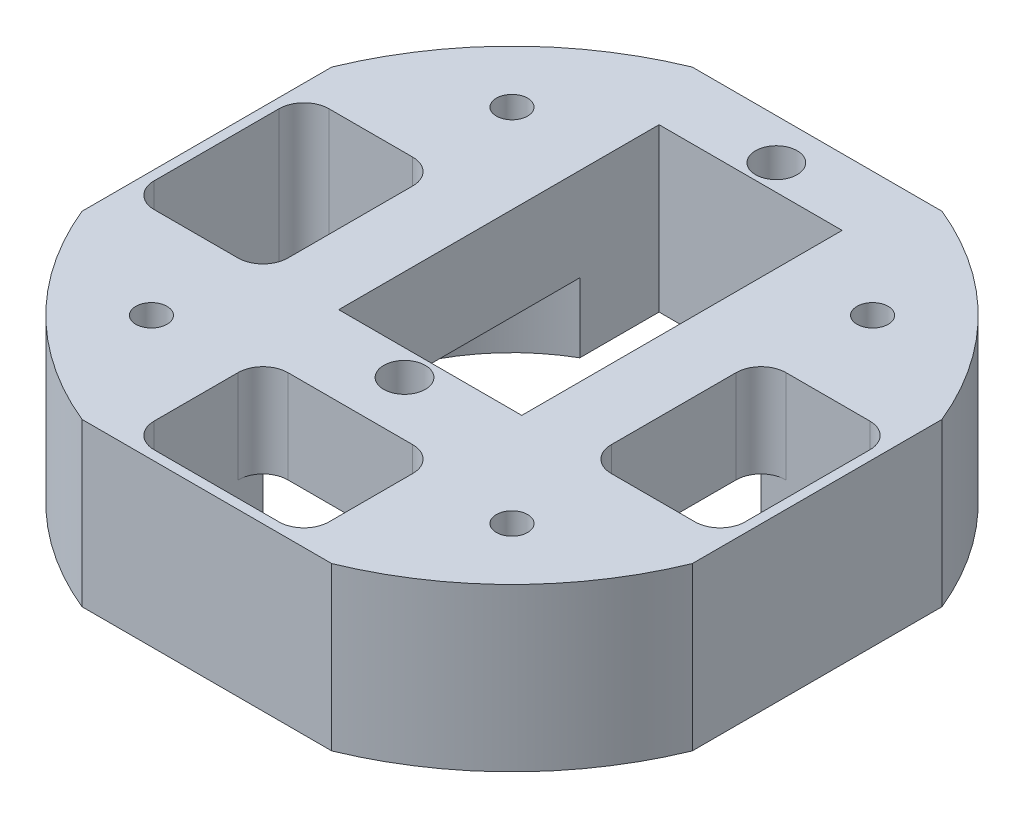
SolidWorks part; units mm, degrees
ref_plane "Front Plane" through (0, 0, 0) normal (0, 0, 1) x (1, 0, 0)
ref_plane "Top Plane" through (0, 0, 0) normal (0, 1, 0) x (1, 0, 0)
ref_plane "Right Plane" through (0, 0, 0) normal (1, 0, 0) x (0, 0, -1)
sketch "Sketch2" plane through (0, 0, 0) normal (0, 1, 0) x (1, 0, 0)
  line L0 (17, -17) -> (-17, -17)
  line L1 (17, -17) -> (17, 17)
  line L2 (17, 17) -> (-17, 17)
  line L3 (-17, -17) -> (-17, 17)
  line L4 (-4.5, -19.5) -> (-1.5, -19.5) construction
  line L5 (-1.5, -19.5) -> (1.5, -19.5) construction
  line L6 (-22, -22) -> (22, -22)
  line L7 (-10.5, 13) -> (-10.5, 17)
  line L8 (-13, 10.5) -> (-17, 10.5)
  line L9 (-10.5, -13) -> (-10.5, -17)
  line L10 (-13, -10.5) -> (-17, -10.5)
  line L11 (10.5, -13) -> (10.5, -17)
  line L12 (13, -10.5) -> (17, -10.5)
  line L13 (13, 10.5) -> (17, 10.5)
  line L14 (10.5, 13) -> (10.5, 17)
  line L15 (-22, -22) -> (-22, 22)
  line L16 (-22, 22) -> (22, 22)
  line L17 (22, -22) -> (22, 22)
  line L18 (-22, -22) -> (22, 22) construction
  line L19 (-22, 22) -> (22, -22) construction
  line L20 (1.5, -19.5) -> (4.5, -19.5) construction
  line L21 (-19.5, 4.5) -> (-19.5, 1.5) construction
  line L22 (-19.5, 1.5) -> (-19.5, -1.5) construction
  line L23 (-19.5, -1.5) -> (-19.5, -4.5) construction
  line L24 (19.5, 4.5) -> (19.5, 1.5) construction
  line L25 (19.5, 1.5) -> (19.5, -1.5) construction
  line L26 (19.5, -1.5) -> (19.5, -4.5) construction
  line L27 (21.3, 4.5) -> (21.3, -4.5)
  line L28 (17.7, 4.5) -> (17.7, -4.5)
  line L29 (-17.7, 4.5) -> (-17.7, -4.5)
  line L31 (-21.3, 4.5) -> (-21.3, -4.5)
  line L32 (-4.5, -17.7) -> (4.5, -17.7)
  line L33 (-4.5, -21.3) -> (4.5, -21.3)
  line L34 (-6.6, 17.205) -> (6.6, 17.205)
  line L35 (6.6, 17.205) -> (6.6, -5.895)
  line L36 (6.6, -5.895) -> (-6.6, -5.895)
  line L37 (-6.6, -5.895) -> (-6.6, 17.205)
  line L38 (0, -5.895) -> (0, -7.75) construction
  line L39 (0, 17.205) -> (0, 19.06) construction
  line L40 (19.5, 6.3) -> (11.6564, 6.3)
  line L41 (19.5, -6.3) -> (11.6564, -6.3)
  line L42 (6.3, -19.5) -> (6.3, -11.6564)
  line L43 (-6.3, -19.5) -> (-6.3, -11.6564)
  line L44 (-19.5, -6.3) -> (-11.6564, -6.3)
  line L45 (-19.5, 6.3) -> (-11.6564, 6.3)
  line L46 (-11.6564, 6.3) -> (-11.6564, -6.3)
  line L47 (11.6564, 6.3) -> (11.6564, -6.3)
  line L48 (-6.3, -11.6564) -> (6.3, -11.6564)
  circle A3 centre (0, 0) radius 13.25
  circle A4 centre (-13, 13) radius 1.125
  circle A5 centre (13, 13) radius 1.125
  circle A6 centre (13, -13) radius 1.125
  circle A7 centre (-13, -13) radius 1.125
  arc A8 (10.5, 13) -> (13, 10.5) centre (13, 13) ccw
  arc A9 (13, -10.5) -> (10.5, -13) centre (13, -13) ccw
  arc A10 (-10.5, -13) -> (-13, -10.5) centre (-13, -13) ccw
  arc A11 (-13, 10.5) -> (-10.5, 13) centre (-13, 13) ccw
  circle A12 centre (0, 0) radius 19.9812
  arc A13 (9, 22) -> (22, 9) centre (0, 0) cw
  arc A14 (22, -9) -> (9, -22) centre (0, 0) cw
  arc A15 (-9, -22) -> (-22, -9) centre (0, 0) cw
  arc A16 (-22, 9) -> (-9, 22) centre (0, 0) cw
  circle A20 centre (0, -7.75) radius 1.5
  circle A21 centre (0, 19.06) radius 1.5
  circle A22 centre (-1.5, -19.5) radius 0.75
  circle A23 centre (1.5, -19.5) radius 0.75
  circle A24 centre (4.5, -19.5) radius 0.75
  circle A25 centre (-4.5, -19.5) radius 0.75
  circle A26 centre (-4.5, -19.5) radius 1
  circle A27 centre (-1.5, -19.5) radius 1
  circle A28 centre (1.5, -19.5) radius 1
  circle A29 centre (4.5, -19.5) radius 1
  circle A38 centre (-19.5, 4.5) radius 0.75
  circle A39 centre (-19.5, 4.5) radius 1
  circle A40 centre (-19.5, 1.5) radius 0.75
  circle A41 centre (-19.5, 1.5) radius 1
  circle A42 centre (-19.5, -1.5) radius 1
  circle A43 centre (-19.5, -1.5) radius 0.75
  circle A45 centre (-19.5, -4.5) radius 0.75
  arc A54 (4.5, -17.7) -> (4.5, -21.3) centre (4.5, -19.5) cw
  arc A55 (-4.5, -17.7) -> (-4.5, -21.3) centre (-4.5, -19.5) ccw
  arc A60 (-17.7, 4.5) -> (-21.3, 4.5) centre (-19.5, 4.5) ccw
  arc A61 (-17.7, -4.5) -> (-21.3, -4.5) centre (-19.5, -4.5) cw
  circle A62 centre (-19.5, -4.5) radius 1
  circle A63 centre (19.5, 4.5) radius 0.75
  circle A64 centre (19.5, 4.5) radius 1
  circle A65 centre (19.5, 1.5) radius 0.75
  circle A66 centre (19.5, 1.5) radius 1
  circle A67 centre (19.5, -1.5) radius 1
  circle A68 centre (19.5, -1.5) radius 0.75
  circle A69 centre (19.5, -4.5) radius 0.75
  arc A70 (21.3, 4.5) -> (17.7, 4.5) centre (19.5, 4.5) ccw
  arc A71 (21.3, -4.5) -> (17.7, -4.5) centre (19.5, -4.5) cw
  circle A72 centre (19.5, -4.5) radius 1
  point P25 (0, 0)
  point P62 (0, -5.895)
  point P68 (-22, 0)
  point P91 (0, -21.3)
  point P92 (0, -22)
  point P93 (-21.3, 0)
  point P98 (21.3, 0)
  point P100 (22, 0)
  dimension "D2" = 2.25
  dimension "D3" = 26
  dimension "D5" = 26.5
  dimension "D6" = 2.5
  dimension "D9" = 23.7697
  dimension "D11" = 2
  dimension "D12" = 1.5
  dimension "D20" = 39.9625
  dimension "D21" = 3
  dimension "D14" = 1.8
  dimension "D1" = 34
  dimension "D7" = 44
  dimension "D8" = 18
  dimension "D10" = 18
  dimension "D13" = 3
  dimension "D15" = 2.5
  dimension "D16" = 2.5
  dimension "D17" = 2.5
  dimension "D18" = 9
  dimension "D19" = 13.2
  dimension "D22" = 7.75
  dimension "D23" = 26.81
  dimension "D24" = 23.1
extrude "Boss-Extrude3" add sketch "Sketch2" along normal blind 11.7 contours A11 L8 L3 L45 A3 L37 L2 L7 | L7 A12 L8 A11 A4 | A16 L3 A12 L2 | L44 A61 L31 A60 L45 A12 L3 A16 L15 A15 | L3 A12 L45 | L44 A12 L3 | A10 L9 L0 L43 A3 L44 L3 L10 | L10 A12 L9 A10 A7 | A15 L0 A12 L3 | A55 L43 A12 L0 A15 L6 A14 L42 A54 L33 | L0 A12 L43 | L42 A12 L0 | A9 L12 L1 L41 A3 L42 L0 L11 | A14 L1 A12 L0 | L11 A12 L12 A9 A6 | L27 A71 L41 A12 L1 A14 L17 A13 L40 A70 | L1 A12 L41 | L40 A12 L1 | A8 L14 L2 L35 A3 L40 L1 L13 | L13 A12 L14 A8 A5 | A13 L2 A12 L1 | A21 A12 L2 L37 L34 L35 | A21 A12 L2 A13 L16 A16 | A3 L35 L36 L37 A20 region at (12.8639, 0, 19.5872) region at (14.9975, 0, 14.9975) region at (17.336, 0, 13.5566) region at (7.7665, 0, 17.6886) region at (11.0948, 0, 11.0948) region at (10.5919, 0, 15) region at (17.6886, 0, 7.7665) region at (-7.7665, 0, 17.6886) region at (-11.0948, 0, 11.0948) region at (0, 0, 11.3279) region at (-14.9975, 0, 14.9975) region at (11.2328, 0, -11) region at (17.6886, 0, -7.7665) region at (14.9975, 0, -14.9975) region at (-14.0639, 0, 14.0639) region at (-21.664, 0, 0) region at (15, 0, -10.5919) region at (12.8639, 0, -19.5872) region at (-17.6886, 0, 7.7665) region at (8.55, 0, -17.2121) region at (-11.2328, 0, -11) region at (-14.9975, 0, -14.9975) region at (-17.6886, 0, -7.7665) region at (-14.0639, 0, -14.0639)
extrude "Cut-Extrude3" cut sketch "Sketch2<9>" along normal blind 5 contours L48 A3 L47 L35 L36 L37 L46 A20 region at (0, 0, 11.3279)
sketch "Sketch2<9>" plane through (0, 0, 0) normal (0, 1, 0) x (1, 0, 0) same geometry as "Sketch2"
fillet "Fillet1" radius 1.8 6 edges at (-11.6564, 8.35, 6.3) (-11.6564, 8.35, -6.3) (6.3, 8.35, 11.6564) (-6.3, 8.35, 11.6564) (11.6564, 8.35, 6.3) (11.6564, 8.35, -6.3)
